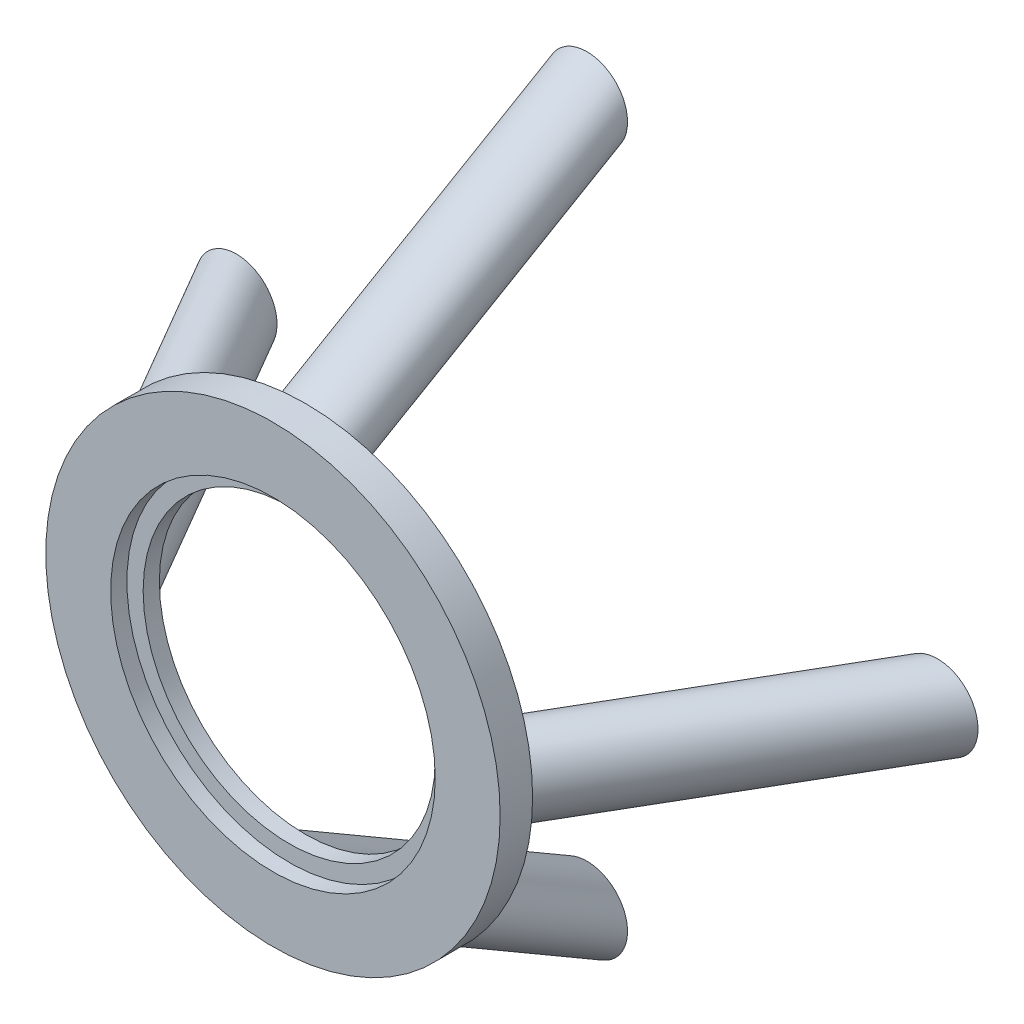
SolidWorks part; units mm, degrees
ref_plane "Front Plane" through (0, 0, 0) normal (0, 0, 1) x (1, 0, 0)
ref_plane "Top Plane" through (0, 0, 0) normal (0, 1, 0) x (1, 0, 0)
ref_plane "Right Plane" through (0, 0, 0) normal (1, 0, 0) x (0, 0, -1)
sketch "Sketch1" plane through (0, 0, 0) normal (0, 0, 1) x (1, 0, 0)
  circle A1 centre (0, 0) radius 70
  circle A2 centre (0, 0) radius 50
  circle A3 centre (0, 0) radius 45
  dimension "D1" = 5
extrude "Boss-Extrude1" add sketch "Sketch1" along normal blind 10 contours A2 | A1
extrude "Boss-Extrude3" add sketch "Sketch1<6>" along normal blind 5 contours A2 A3 region at (-48.5858, 0, 0)
sketch "Sketch1<6>" plane through (0, 0, 0) normal (0, 0, 1) x (1, 0, 0) same geometry as "Sketch1"
sketch "Sketch2" plane through (0, 0, 0) normal (0, 0, -1) x (-1, 0, 0)
  circle A0 centre (0, -57.5) radius 12.5
  circle A1 centre (0, 0) radius 70 construction
  circle A2 centre (0, 0) radius 45 construction
sketch "Sketch3" plane through (0, 0, 0) normal (1, 0, 0) x (0, 0, -1)
  line L1 (0, -70) -> (0, -45) construction
  line L2 (0, -57.5) -> (86.7319, -107.983)
  point P8 (0, -57.5)
sweep "Sweep1" add profiles "Sketch2" path "Sketch3"
pattern_circular "CirPattern2" count 4 over 360 about axis through (0, 0, 10) along (0, 0, -1) of "Sweep1"
sketch "Sketch8" plane through (0, 0, 0) normal (0, 0, -1) x (-1, 0, 0)
  line L0 (-42.4264, 38.8909) -> (-38.8909, 42.4264)
  line L17 (-42.4264, 38.8909) -> (-38.8909, 35.3553)
  line L18 (-38.8909, 35.3553) -> (-35.3553, 38.8909)
  line L19 (-38.8909, 42.4264) -> (-42.4264, 38.8909)
  line L20 (-38.8909, 42.4264) -> (-42.4264, 45.9619)
  line L21 (-42.4264, 45.9619) -> (-45.9619, 42.4264)
  line L22 (-42.4264, 38.8909) -> (-45.9619, 42.4264)
  line L23 (-38.8909, 42.4264) -> (-35.3553, 38.8909)
  point P6 (-40.6586, 40.6586)
  point P16 (0, 0)
extrude "Cut-Extrude5" cut sketch "Sketch8" against normal blind 2 contours L23 L0 L17 L18 region at (38.8909, 38.8909, 0)
extrude "Cut-Extrude8" cut sketch "Sketch8<6>" against normal blind 1 from offset 1 contours L22 L0 L20 L21 region at (42.4264, 42.4264, 0) offset against normal yes
sketch "Sketch8<6>" plane through (0, 0, 0) normal (0, 0, -1) x (-1, 0, 0) same geometry as "Sketch8"
pattern_circular "CirPattern4" count 4 over 360 about axis through (0, 0, 10) along (0, 0, -1) of "Cut-Extrude8", "Cut-Extrude5"
